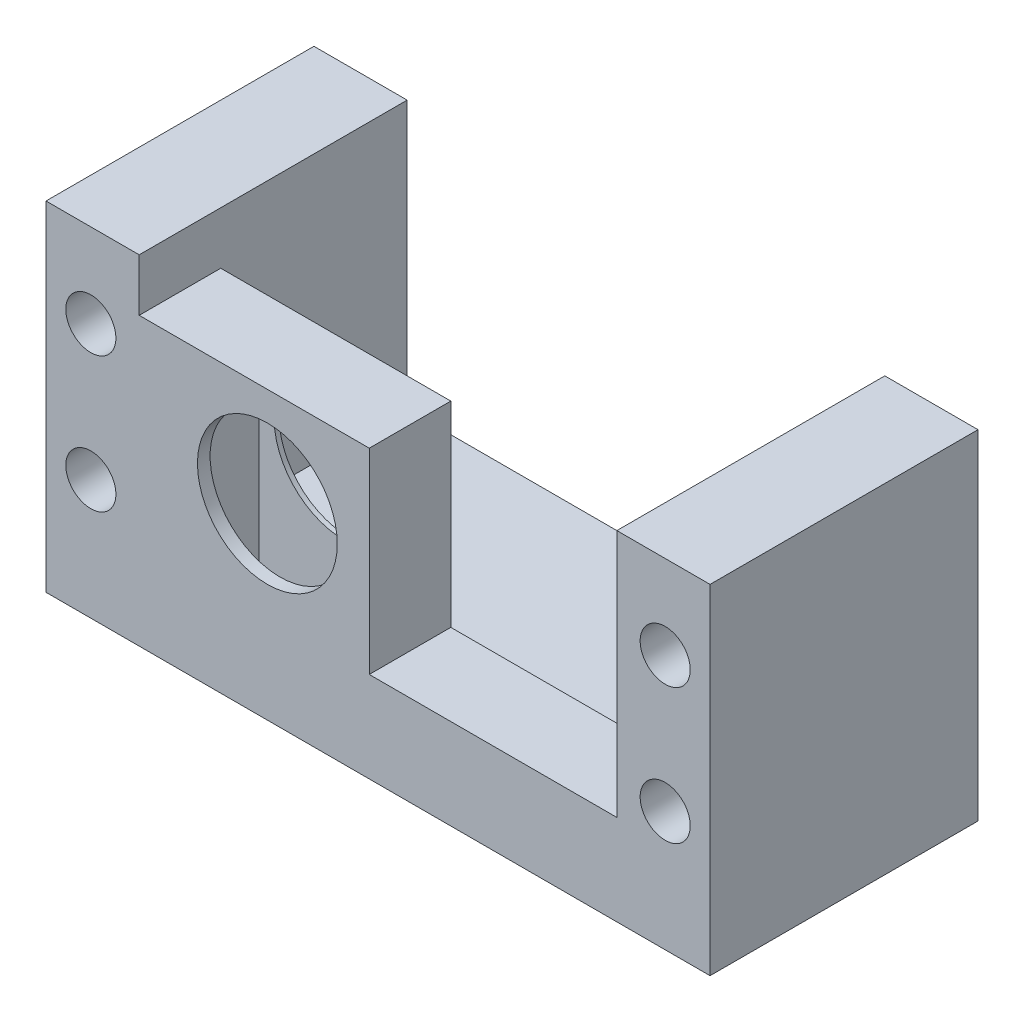
SolidWorks part; units mm, degrees
ref_plane "Спереди" through (0, 0, 0) normal (0, 0, 1) x (1, 0, 0)
ref_plane "Сверху" through (0, 0, 0) normal (0, 1, 0) x (1, 0, 0)
ref_plane "Справа" through (0, 0, 0) normal (1, 0, 0) x (0, 0, -1)
sketch "Эскиз1" plane through (0, 0, 0) normal (0, 0, 1) x (1, 0, 0)
  line L2 (-59.1906, -40.1769) -> (-59.1906, -15.0857)
  line L3 (-59.1906, -15.0857) -> (-51.1906, -15.0857)
  line L4 (-2.1906, -38.0857) -> (-2.1906, -15.0857)
  line L8 (-2.1906, -15.0857) -> (-10.1906, -15.0857)
  line L9 (-10.1906, -15.0857) -> (-10.1906, -38.0857)
  line L10 (-51.1906, -15.0857) -> (-51.1906, -38.0857)
  line L11 (-51.1906, -38.0857) -> (-10.1906, -38.0857)
  line L12 (-59.1906, -40.1769) -> (-59.1906, -44.1769)
  line L13 (-59.1906, -44.1769) -> (-2.1906, -44.1769)
  line L14 (-2.1906, -44.1769) -> (-2.1906, -38.0857)
  point P0 (0, 0)
extrude "Бобышка-Вытянуть1" add sketch "Эскиз1" along normal blind 23
sketch "Эскиз3" plane through (-59.1906, 0, 0) normal (-1, 0, 0) x (0, 0, 1)
  line L5 (0, -15.0857) -> (0, -44.1769) construction
  line L6 (15, -15.0857) -> (0, -15.0857) construction
  line L7 (15, -15.0857) -> (15, -38.2478) construction
  line L8 (15, -38.2478) -> (0, -38.2478) construction
  line L9 (0, -15.0857) -> (0, -38.2478) construction
sketch "Эскиз5" plane through (0, 0, 23) normal (0, 0, 1) x (1, 0, 0)
  line L0 (-51.1906, -38.0857) -> (-51.1906, -15.0857) construction
  line L1 (-10.1906, -28.0857) -> (-24.1906, -28.0857) construction
  line L6 (-30.6906, -18.0857) -> (-30.6906, -34.9839) construction
  line L11 (-51.1906, -28.0857) -> (-37.1906, -28.0857) construction
  line L12 (-10.1906, -38.0857) -> (-51.1906, -38.0857) construction
  line L13 (-10.1906, -38.0857) -> (-10.1906, -18.0857) construction
  line L14 (-10.1906, -18.0857) -> (-51.1906, -18.0857) construction
  line L15 (-51.1906, -38.0857) -> (-51.1906, -18.0857) construction
  line L16 (-21.1906, -34.9839) -> (-51.1906, -34.9839) construction
  line L18 (-21.1906, -19.5857) -> (-51.1906, -19.5857)
  line L19 (-51.1906, -34.9839) -> (-51.1906, -19.5857)
  line L20 (-21.1906, -19.5857) -> (-10.1906, -19.5857)
  line L22 (-21.1906, -34.9839) -> (-10.1906, -34.9839) construction
  line L23 (-10.1906, -19.5857) -> (-10.1906, -34.9839)
  line L24 (-10.1906, -38.0857) -> (-51.1906, -38.0857)
  line L25 (-51.1906, -38.0857) -> (-51.1906, -34.9839)
  line L26 (-10.1906, -38.0857) -> (-10.1906, -34.9839)
  circle A5 centre (-21.1906, -28.0857) radius 2.7
  circle A6 centre (-40.1906, -28.0857) radius 6
extrude "Бобышка-Вытянуть6" add sketch "Эскиз5" against normal blind 7
sketch "Эскиз6" plane through (0, 0, 23) normal (0, 0, 1) x (1, 0, 0)
  line L0 (-51.1906, -19.5857) -> (-51.1906, -15.0857) construction
  line L3 (-10.1906, -18.0857) -> (-51.1906, -18.0857)
  line L4 (-51.1906, -38.0857) -> (-51.1906, -18.0857)
  line L5 (-2.1906, -38.0857) -> (-59.1906, -38.0857) construction
  line L6 (-2.1906, -44.1769) -> (-2.1906, -15.0857) construction
  line L7 (-6.0406, -38.0857) -> (-6.0406, -29.5857) construction
  line L8 (-59.1906, -15.0857) -> (-59.1906, -44.1769) construction
  line L9 (-10.1906, -18.0857) -> (-2.1906, -18.0857) construction
  line L10 (-6.0406, -18.0857) -> (-6.0406, -26.5857) construction
  line L11 (-6.0406, -22.2857) -> (-10.1906, -22.2857) construction
  line L12 (-30.6906, -38.0857) -> (-30.6906, -18.0857) construction
  line L13 (-10.1906, -18.0857) -> (-10.1906, -38.0857) construction
  line L14 (-6.0406, -33.8857) -> (-10.1906, -33.8857) construction
  circle A1 centre (-6.0406, -33.8857) radius 2.15
  circle A3 centre (-6.0406, -22.2857) radius 2.15
  circle A4 centre (-55.3406, -22.2857) radius 2.15
  circle A5 centre (-55.3406, -33.8857) radius 2.15
extrude "Вырез-Вытянуть2" cut sketch "Эскиз6" against normal through all contours A1 | A3 | A5 | A4 region at (-6.0406, -33.8857, 23) region at (-6.0406, -22.2857, 23) region at (-55.3406, -22.2857, 23) region at (-55.3406, -33.8857, 23)
sketch "Эскиз8" plane through (0, 0, 23) normal (0, 0, 1) x (1, 0, 0)
  line L1 (-10.1906, -19.5857) -> (-31.4429, -19.5857)
  line L2 (-10.1906, -19.5857) -> (-10.1906, -36.4088)
  line L3 (-10.1906, -36.4088) -> (-31.4429, -36.4088)
  line L4 (-31.4429, -19.5857) -> (-31.4429, -36.4088)
extrude "Вырез-Вытянуть4" cut sketch "Эскиз8" against normal up to surface (7 mm away) up to face at (-46.1906, -28.0857, 16)
sketch "Эскиз16" plane through (0, 0, 23) normal (0, 0, 1) x (1, 0, 0)
  line L0 (-40.1906, -21.4357) -> (-40.1906, -34.7357)
  line L1 (-40.1906, -21.4357) -> (-43.9534, -21.4357) construction
  line L2 (-43.9534, -21.4357) -> (-43.9534, -44.1769) construction
  line L3 (-59.1906, -44.1769) -> (-2.1906, -44.1769) construction
  line L4 (-40.1906, -28.0857) -> (-40.1906, -44.1769) construction
  line L5 (-40.1906, -44.1769) -> (-39.0508, -41.093) construction
  point P4 (-40.1906, -28.0857)
sketch "Эскиз14" plane through (0, -44.1769, 0) normal (0, -1, 0) x (-1, 0, 0)
  line L0 (40.2278, -23) -> (40.2278, -19.1629) construction
  line L1 (59.1906, -23) -> (2.1906, -23) construction
  line L3 (32.9778, -21.9129) -> (47.4778, -21.9129)
  line L4 (32.9778, -21.9129) -> (32.9778, -16.4129)
  line L5 (32.9778, -16.4129) -> (47.4778, -16.4129)
  line L6 (47.4778, -21.9129) -> (47.4778, -16.4129)
  line L7 (32.9778, -21.9129) -> (47.4778, -16.4129) construction
  line L8 (32.9778, -16.4129) -> (47.4778, -21.9129) construction
extrude "Вырез-Вытянуть7" cut sketch "Эскиз14" against normal blind 22.74
